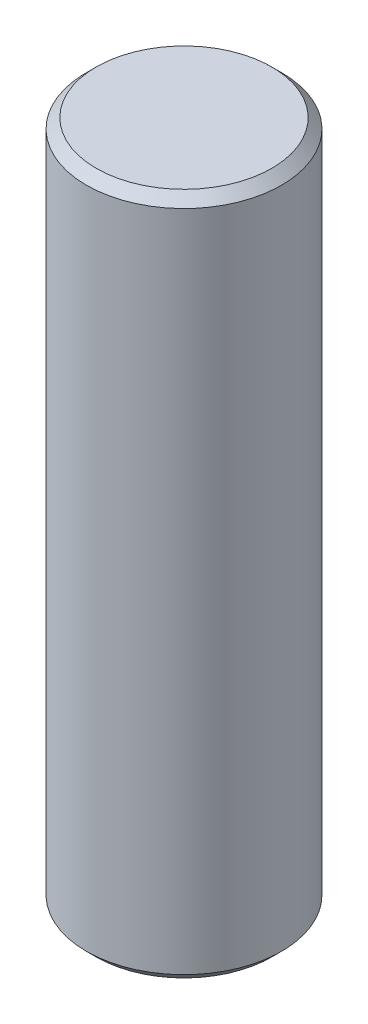
SolidWorks part; units mm, degrees
material "6061-T6 (SS)"
ref_plane "Front Plane" through (0, 0, 0) normal (0, 0, 1) x (1, 0, 0)
ref_plane "Top Plane" through (0, 0, 0) normal (0, 1, 0) x (1, 0, 0)
ref_plane "Right Plane" through (0, 0, 0) normal (1, 0, 0) x (0, 0, -1)
ref_axis "CentralAxis" through (0, 1.1, 0) along (0, -1, 0)
sketch "BaseS" plane through (0, 0, 0) normal (0, 1, 0) x (1, 0, 0)
  circle A0 centre (0, 0) radius 2
  dimension "Diameter" = 4
extrude "Base" add sketch "BaseS" along normal mid plane 14
chamfer "BaseChamfer" distance 0.2 angle 45 2 edges at (0, -7, 2) (0, 7, 2)
